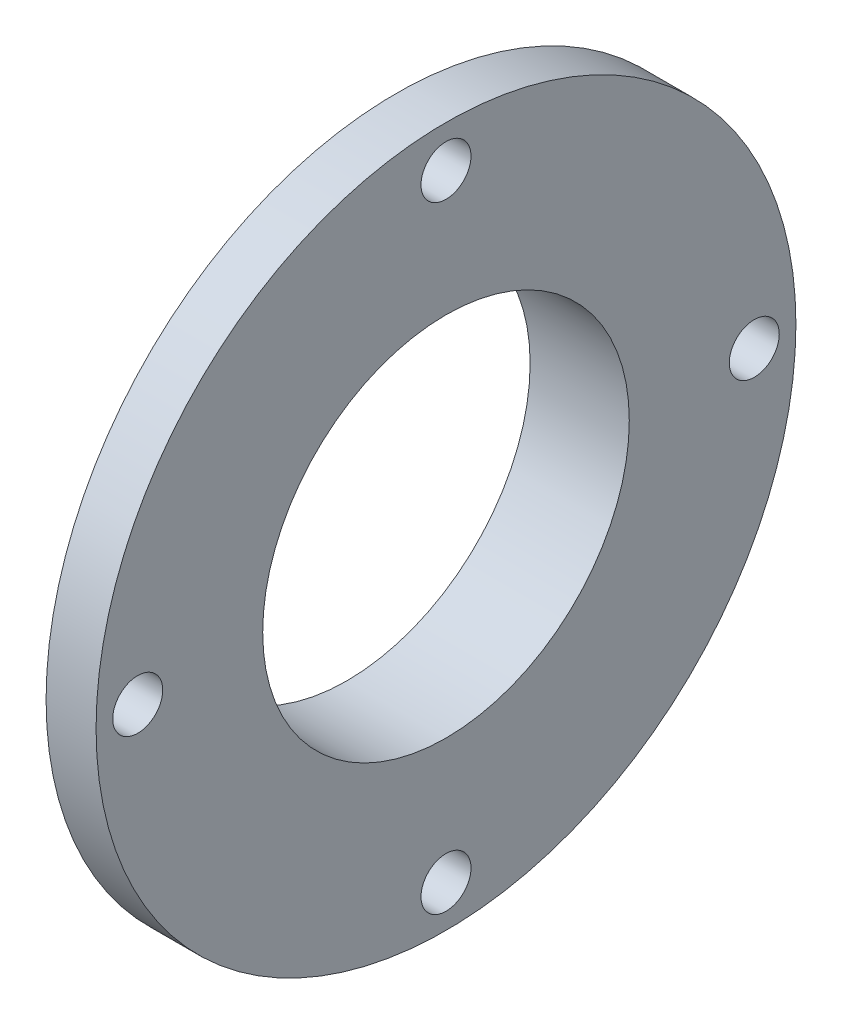
SolidWorks part; units mm, degrees
material "2024-T4"
ref_plane "Front Plane" through (0, 0, 0) normal (0, 0, 1) x (1, 0, 0)
ref_plane "Top Plane" through (0, 0, 0) normal (0, 1, 0) x (1, 0, 0)
ref_plane "Right Plane" through (0, 0, 0) normal (1, 0, 0) x (0, 0, -1)
sketch "Sketch1" plane through (0, 0, 0) normal (1, 0, 0) x (0, 0, -1)
  circle A0 centre (0, 0) radius 21
  circle A1 centre (0, 0) radius 11
  circle A2 centre (0, 0) radius 18.5 construction
  circle A3 centre (0, 18.5) radius 1.5
  circle A4 centre (18.5, 0) radius 1.5
  circle A5 centre (0, -18.5) radius 1.5
  circle A6 centre (-18.5, 0) radius 1.5
  point P15 (0, 0)
  dimension "D1" = 22
  dimension "D2" = 42
  dimension "D3" = 37
  dimension "D4" = 3
  dimension "D5" = 4
extrude "Boss-Extrude1" add sketch "Sketch1" along normal blind 3
sketch "Sketch2" plane through (0, 0, 0) normal (-1, 0, 0) x (0, 0, 1)
  circle A0 centre (0, 0) radius 16
  circle A1 centre (0, 0) radius 11 construction
  circle A2 centre (0, 0) radius 11
  dimension "D1" = 32
extrude "Boss-Extrude2" add sketch "Sketch2" along normal blind 2.95
